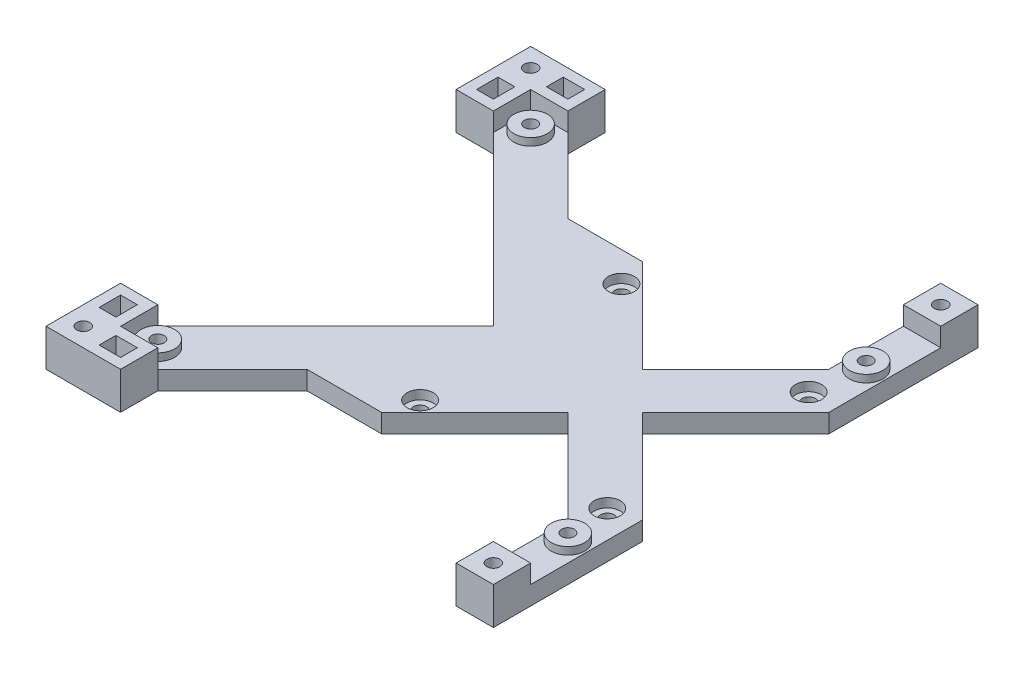
SolidWorks part; units mm, degrees
ref_plane "Plan de face" through (0, 0, 0) normal (0, 0, 1) x (1, 0, 0)
ref_plane "Plan de dessus" through (0, 0, 0) normal (0, 1, 0) x (1, 0, 0)
ref_plane "Plan de droite" through (0, 0, 0) normal (1, 0, 0) x (0, 0, -1)
sketch "Esquisse1" plane through (0, 0, 0) normal (0, 1, 0) x (1, 0, 0)
  line L0 (55, 35) -> (-10.084, 35) construction
  line L1 (55, 35) -> (55, -35) construction
  line L2 (55, -35) -> (-10.084, -35) construction
  line L3 (-10.084, 35) -> (-10.084, -35) construction
  line L4 (-10.084, 35) -> (55, -35) construction
  line L5 (55, 35) -> (-10.084, -35) construction
  line L6 (-25, -35) -> (-5, -35)
  line L7 (-55, -55) -> (55, -55) construction
  line L8 (-55, -55) -> (-55, 55) construction
  line L9 (-55, 55) -> (55, 55) construction
  line L10 (55, -55) -> (55, 55) construction
  line L11 (-55, -55) -> (55, 55) construction
  line L12 (-55, 55) -> (55, -55) construction
  line L13 (-25, -35) -> (-45, -55)
  line L14 (-45, -55) -> (-55, -55)
  line L15 (-55, -55) -> (-55, -45)
  line L16 (-55, -45) -> (-10.084, -0.084)
  line L17 (55, -35) -> (55, -25)
  line L18 (-5, -35) -> (20, -10)
  line L19 (20, -10) -> (45, -35)
  line L21 (55, -25) -> (30, 0)
  line L22 (-10.084, -0.084) -> (-10.084, 0.084)
  line L23 (-10.084, 0) -> (30, 0) construction
  line L24 (55, 25) -> (30, 0)
  line L25 (55, 35) -> (55, 25)
  line L27 (20, 10) -> (45, 35)
  line L28 (-5, 35) -> (20, 10)
  line L29 (-25, 35) -> (-5, 35)
  line L30 (-25, 35) -> (-45, 55)
  line L31 (-45, 55) -> (-55, 55)
  line L32 (-55, 55) -> (-55, 45)
  line L33 (-55, 45) -> (-10.084, 0.084)
  line L34 (45, 35) -> (45, 55)
  line L35 (45, 55) -> (55, 55)
  line L36 (55, 55) -> (55, 35)
  line L37 (45, -35) -> (45, -55)
  line L38 (45, -55) -> (55, -55)
  line L39 (55, -35) -> (55, -55)
  circle A0 centre (-50, 50) radius 1.65 construction
  circle A1 centre (-50, -50) radius 1.65 construction
  circle A2 centre (50, -40) radius 1.65 construction
  circle A3 centre (50, 40) radius 1.65 construction
  point P4 (0, 0)
  dimension "D1" = 10
  dimension "D2" = 10
  dimension "D3" = 10
  dimension "D4" = 10
  dimension "D5" = 90
  dimension "D6" = 90
  dimension "D7" = 90
  dimension "D8" = 90
  dimension "D10" = 0
  dimension "D11" = 110
  dimension "D12" = 110
  dimension "D13" = 0
extrude "Boss.-Extru.1" add sketch "Esquisse1" along normal blind 5
sketch "Esquisse2" plane through (0, 0, 0) normal (0, 1, 0) x (1, 0, 0)
  line L0 (-55, -45) -> (-65, -45)
  line L1 (-65, -45) -> (-65, -65)
  line L2 (-65, -65) -> (-45, -65)
  line L3 (-45, -65) -> (-45, -55)
  line L4 (0, 0) -> (-80.1465, 0) construction
  line L5 (-55, -45) -> (-55, -55)
  line L14 (-55, -55) -> (-45, -55)
  line L19 (-45, 65) -> (-45, 55)
  line L20 (-65, 65) -> (-45, 65)
  line L21 (-65, 45) -> (-65, 65)
  line L22 (-55, 55) -> (-45, 55)
  line L23 (-55, 45) -> (-55, 55)
  line L24 (-55, 45) -> (-65, 45)
  line L25 (55, 55) -> (45, 55) construction
  line L26 (45, 55) -> (55, 55)
  line L27 (45, 55) -> (45, 65)
  line L28 (45, 65) -> (55, 65)
  line L29 (55, 55) -> (55, 65)
  line L30 (45, -55) -> (55, -55)
  line L31 (45, -55) -> (45, -65)
  line L32 (45, -65) -> (55, -65)
  line L33 (55, -55) -> (55, -65)
  line L34 (55, -55) -> (55, -25) construction
  line L35 (55, 25) -> (55, 55) construction
  line L36 (-55, 55) -> (-65, 65) construction
  line L37 (-55, -55) -> (-65, -65) construction
  line L39 (-65, -55) -> (-55, -65) construction
  line L40 (-65, 55) -> (-55, 65) construction
  dimension "D1" = 10
  dimension "D2" = 90
  dimension "D3" = 10
  dimension "D4" = 10
  dimension "D5" = 10
  dimension "D6" = 0
  dimension "D7" = 0
extrude "Boss.-Extru.2" add sketch "Esquisse2" along normal blind 10
sketch "Esquisse3" plane through (0, 5, 0) normal (0, 1, 0) x (1, 0, 0)
  line L0 (0, 0) -> (50, 40) construction
  line L1 (0, 0) -> (50, -40) construction
  line L2 (0, 0) -> (-50, 50) construction
  line L3 (0, 0) -> (-50, -50) construction
  circle A0 centre (-50, -50) radius 4.5
  circle A1 centre (-50, 50) radius 4.5
  circle A2 centre (50, 40) radius 4.5
  circle A3 centre (50, -40) radius 4.5
  dimension "D9" = 9
  dimension "D10" = 9
  dimension "D11" = 9
  dimension "D12" = 9
  dimension "D1" = 50
  dimension "D2" = 40
  dimension "D3" = 40
  dimension "D4" = 50
  dimension "D5" = 50
  dimension "D6" = 50
  dimension "D7" = 50
  dimension "D8" = 50
extrude "Boss.-Extru.3" add sketch "Esquisse3" along normal blind 2
sketch "Esquisse5" plane through (0, 7, 0) normal (0, 1, 0) x (1, 0, 0)
  point P0 (-50, 50)
  point P1 (50, 40)
  point P3 (50, -40)
  point P5 (-50, -50)
hole_wizard "Dégagement M31" positions "Esquisse3D2" profile "Esquisse6" hole size "M3" standard "Ansi Metric" end condition through all
sketch3d "Esquisse3D2"
  point P0 (-50, 7, -50)
  point P3 (50, 7, -40)
  point P6 (50, 7, 40)
  point P9 (-50, 7, 50)
sketch "Esquisse6" plane through (-50, 7, -50) normal (1, 0, 0) x (0, 0, 1)
  line L0 (0, 0) -> (0, 7)
  line L1 (0, 7) -> (1.7, 7)
  line L2 (1.7, 7) -> (1.7, 0)
  line L5 (1.7, 0) -> (0, 0)
  line L11 (0, -6.35) -> (0, 107.95) construction
  dimension "Diamètre du perçage jusqu'au prochain" = 3.4
  dimension "Profondeur du perçage jusqu'au prochain" = 7
sketch "Esquisse7" plane through (0, 5, 0) normal (0, 1, 0) x (1, 0, 0)
  line L0 (-10.084, 0.084) -> (-10.084, -0.084) construction
  line L1 (-10.084, -35) -> (55, -35) construction
  line L2 (-10.084, -35) -> (-10.084, 35) construction
  line L3 (-10.084, 35) -> (55, 35) construction
  line L4 (55, -35) -> (55, 35) construction
  line L5 (55, 25) -> (55, 55) construction
  line L6 (-5, 35) -> (-25, 35) construction
  line L7 (-25, -35) -> (-5, -35) construction
  line L8 (-10.084, 35) -> (55, -35) construction
  line L9 (-10.084, -35) -> (55, 35) construction
  point P5 (47.5618, 27)
  point P14 (47.5618, -27)
  point P15 (-2.6458, -27)
  point P22 (-2.6458, 27)
  dimension "D1" = 0
  dimension "D2" = 0
  dimension "D3" = 0
  dimension "D4" = 0
  dimension "D5" = 54
  dimension "D6" = 27
  dimension "D7" = 27
hole_wizard "Chambrage pour vis à tête ronde bombée M32" positions "Esquisse3D3" profile "Esquisse8" counterbore size "M3" standard "Ansi Metric" end condition through all
sketch3d "Esquisse3D3"
  point P0 (-2.6458, 5, -27)
  point P3 (-2.6458, 5, 27)
  point P6 (47.5618, 5, 27)
  point P9 (47.5618, 5, -27)
sketch "Esquisse8" plane through (-2.6458, 5, -27) normal (1, 0, 0) x (0, 0, 1)
  line L0 (0, 0) -> (0, 5)
  line L1 (0, 5) -> (1.8, 5)
  line L3 (1.8, 5) -> (1.8, 2.4)
  line L4 (1.8, 2.4) -> (3.5, 2.4)
  line L5 (3.5, 2.4) -> (3.5, 0)
  line L7 (3.5, 0) -> (0, 0)
  line L11 (0, -6.35) -> (0, 107.95) construction
  dimension "Diamètre du perçage jusqu'au prochain" = 3.6
  dimension "Profondeur du perçage jusqu'au prochain" = 5
  dimension "Diamètre du chambrage" = 7
  dimension "Profondeur du chambrage" = 2.4
sketch "Esquisse10" plane through (0, 0, 0) normal (0, 1, 0) x (1, 0, 0)
  line L24 (-55, -55) -> (55, -55) construction
  line L29 (-55, -55) -> (-55, 55) construction
  line L30 (-55, 55) -> (55, 55) construction
  line L31 (55, 55) -> (55, -55) construction
  line L39 (-55, 55) -> (-45, 55) construction
  line L50 (-55, 55) -> (-55, 45) construction
  line L70 (108.7528, -114.7101) -> (134.7336, -99.7101) construction
  line L71 (-76.0746, 22) -> (-74.4346, 22) construction
  line L72 (-76.0746, 22) -> (-76.0746, -8) construction
  line L73 (-76.0746, -8) -> (-74.4346, -8) construction
  line L74 (-74.4346, 22) -> (-74.4346, -8) construction
  line L75 (115.271, -110) -> (115.271, 110) construction
  line L76 (115.271, 110) -> (-75.2546, 0) construction
  line L77 (-75.2546, 0) -> (115.271, -110) construction
  line L82 (134.7336, -99.7101) -> (133.9136, -98.2899) construction
  line L83 (133.9136, -98.2899) -> (107.9328, -113.2899) construction
  line L84 (107.9328, -113.2899) -> (108.7528, -114.7101) construction
  line L85 (108.7364, 114.6873) -> (131.2036, 94.807) construction
  line L86 (131.2036, 94.807) -> (132.2903, 96.0352) construction
  line L87 (132.2903, 96.0352) -> (109.8232, 115.9155) construction
  line L88 (109.8232, 115.9155) -> (108.7364, 114.6873) construction
  circle A4 centre (-75.2546, 0) radius 5 construction
  circle A5 centre (115.271, 110) radius 5 construction
  circle A6 centre (115.271, -110) radius 5 construction
  circle A7 centre (120.91, -126.83) radius 3.15 construction
  circle A8 centre (157, -129.7) radius 3.15 construction
  circle A9 centre (120.91, 126.83) radius 3.15 construction
  circle A10 centre (157, 129.7) radius 3.15 construction
  circle A11 centre (51.7625, 0) radius 63.5085 construction
  dimension "D9" = 5.639
  dimension "D12" = 16.83
  dimension "D13" = 5.639
  dimension "D14" = 36.09
  dimension "D27" = 8
  dimension "D31" = 1.64
  dimension "D32" = 0.82
  dimension "D33" = 8
  dimension "D1" = 60.271
  dimension "D2" = 106.7625
  dimension "D3" = 60
  dimension "D4" = 60
  dimension "D5" = 60
  dimension "D6" = 110
  dimension "D7" = 110
  dimension "D8" = 16.83
  dimension "D10" = 36.09
  dimension "D11" = 2.87
  dimension "D15" = 2.87
  dimension "D16" = 0
  dimension "D17" = 0
  dimension "D18" = 0
  dimension "D19" = 0
  dimension "D20" = 1.64
  dimension "D21" = 8
  dimension "D22" = 0.82
  dimension "D23" = 1.64
  dimension "D24" = 30
  dimension "D25" = 30
  dimension "D26" = 51.7625
  dimension "D28" = 0.82
  dimension "D29" = 60
  dimension "D30" = 30
sketch "Esquisse11" plane through (0, 10, 0) normal (0, 1, 0) x (1, 0, 0)
  line L0 (-55, -55) -> (-65, -65) construction
  line L1 (-55, 55) -> (-65, 65) construction
  line L2 (55, 65) -> (45, 55) construction
  line L3 (45, -55) -> (55, -65) construction
  circle A0 centre (-60, 60) radius 1.75
  circle A1 centre (50, 60) radius 1.75
  circle A2 centre (50, -60) radius 1.75
  circle A3 centre (-60, -60) radius 1.75
  dimension "D1" = 3.5
  dimension "D2" = 3.5
  dimension "D3" = 3.5
  dimension "D4" = 3.5
extrude "Enlèv. mat.-Extru.1" cut sketch "Esquisse11" against normal blind 10
sketch "Esquisse14" plane through (0, 10, 0) normal (0, 1, 0) x (1, 0, 0)
  line L0 (-55, 55) -> (55, 55) construction
  line L1 (-53.5, 57.75) -> (-47.75, 57.75)
  line L2 (-53.5, 57.75) -> (-53.5, 62.25)
  line L3 (-53.5, 62.25) -> (-47.75, 62.25)
  line L4 (-47.75, 57.75) -> (-47.75, 62.25)
  line L5 (-62.25, 53.5) -> (-57.75, 53.5)
  line L6 (-62.25, 53.5) -> (-62.25, 47.75)
  line L7 (-62.25, 47.75) -> (-57.75, 47.75)
  line L8 (-57.75, 53.5) -> (-57.75, 47.75)
  line L9 (-45, 65) -> (-65, 65) construction
  line L10 (-55, -55) -> (-55, 55) construction
  line L11 (-65, 65) -> (-65, 45) construction
  line L12 (-65, 45) -> (-55, 45) construction
  line L13 (-45, 55) -> (-45, 65) construction
  line L14 (0, 0) -> (-92.4316, 0) construction
  line L15 (-57.75, -53.5) -> (-57.75, -47.75)
  line L16 (-62.25, -47.75) -> (-57.75, -47.75)
  line L17 (-62.25, -53.5) -> (-62.25, -47.75)
  line L18 (-62.25, -53.5) -> (-57.75, -53.5)
  line L19 (-47.75, -57.75) -> (-47.75, -62.25)
  line L20 (-53.5, -62.25) -> (-47.75, -62.25)
  line L21 (-53.5, -57.75) -> (-53.5, -62.25)
  line L22 (-53.5, -57.75) -> (-47.75, -57.75)
  point P18 (-60, 45)
  dimension "D1" = 2.75
  dimension "D2" = 2.75
  dimension "D3" = 2.75
  dimension "D4" = 2.75
  dimension "D5" = 2.75
  dimension "D6" = 2.75
  dimension "D7" = 1.5
  dimension "D8" = 1.5
extrude "Enlèv. mat.-Extru.2" cut sketch "Esquisse14" against normal blind 5
